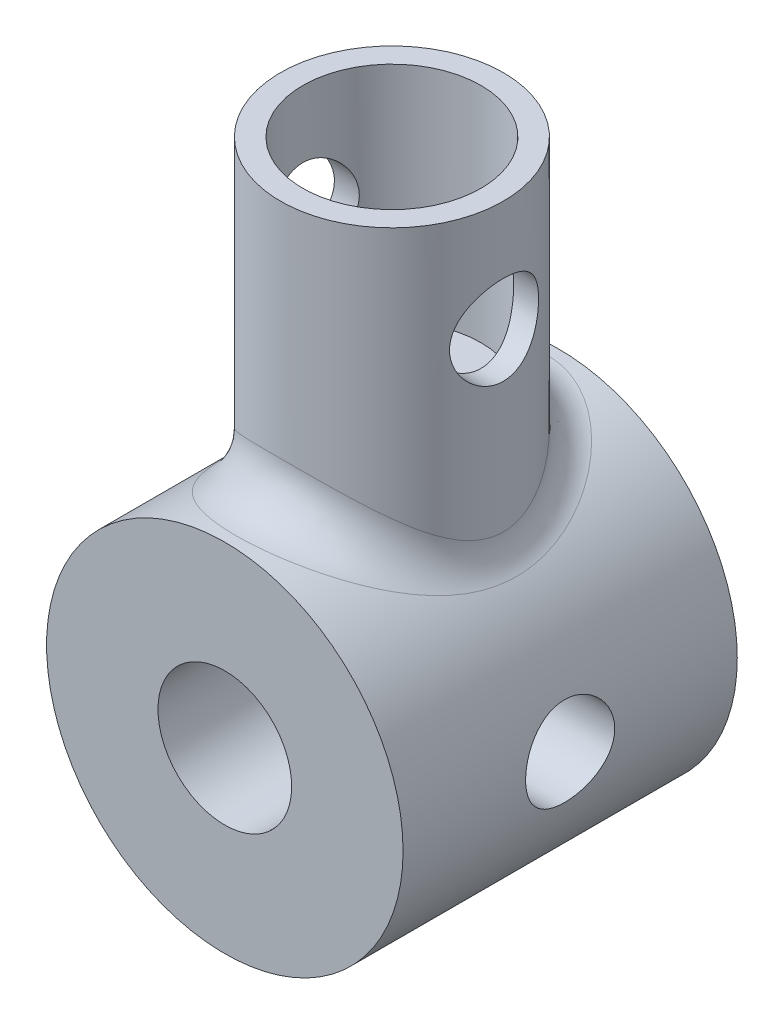
SolidWorks part; units mm, degrees
ref_plane "Front" through (0, 0, 0) normal (0, 0, 1) x (1, 0, 0)
ref_plane "Top" through (0, 0, 0) normal (0, 1, 0) x (1, 0, 0)
ref_plane "Right" through (0, 0, 0) normal (1, 0, 0) x (0, 0, -1)
sketch "Sketch1" plane through (0, 0, 0) normal (0, 0, 1) x (1, 0, 0)
  line L0 (0, 0) -> (0, 400) construction
  line L1 (-5, 0) -> (-5, 400)
  line L2 (5, 0) -> (5, 400)
  line L3 (0, -5) -> (0, 405)
  circle A0 centre (0, 0) radius 3
  circle A1 centre (0, 0) radius 8
  arc A2 (-5, 0) -> (5, 0) centre (0, 0) ccw
  arc A3 (5, 400) -> (-5, 400) centre (0, 400) ccw
  point P5 (0, 200)
  dimension "D1" = 6
  dimension "D4" = 5
  dimension "D3" = 400
  dimension "D2" = 5
extrude "Boss-Extrude1" add sketch "Sketch1" along normal mid plane 15 contours A2 L1 A1 L2 | L3 A2 L2 A1 A0 | L1 A2 L3 A0 A1 region at (-3.687, -3.687, 0) region at (-2.6489, 2.2826, 0) region at (2.6489, 2.2826, 0)
sketch "Sketch3" plane through (0, 0, 0) normal (0, 0, 1) x (1, 0, 0)
  line L1 (-10, 399) -> (10, 399)
  line L2 (-10, 399) -> (-10, 429)
  line L3 (-10, 429) -> (10, 429)
  line L4 (10, 399) -> (10, 429)
  line L5 (-10, 399) -> (10, 429) construction
  line L6 (-10, 429) -> (10, 399) construction
  point P0 (0, 414)
  dimension "D1" = 30
  dimension "D2" = 20
  dimension "D3" = 399
extrude "Boss-Extrude2" add sketch "Sketch3" along normal mid plane 15
revolve "Revolve2" add sketch "Sketch1<7>" angle 360 about L0 region at (2.4981, 205.6864, 0)
sketch "Sketch1<7>" plane through (0, 0, 0) normal (0, 0, 1) x (1, 0, 0) same geometry as "Sketch1"
combine bodies "Combine1" operation type add bodies to combine 106 101
fillet "Fillet1" radius 2 2 edges at (0, 399, 5) (1.219, 7.9066, 4.8491)
sketch "Sketch5" plane through (0, 429, 0) normal (0, 1, 0) x (1, 0, 0)
  line L0 (8, 5.5) -> (-8, 5.5)
  line L1 (-8, 5.5) -> (-8, -5.5)
  line L2 (-8, -5.5) -> (8, -5.5)
  line L3 (8, -5.5) -> (8, 5.5)
  line L4 (10, 7.5) -> (-10, 7.5)
  line L5 (-10, 7.5) -> (-10, -7.5)
  line L6 (-10, -7.5) -> (10, -7.5)
  line L7 (10, -7.5) -> (10, 7.5)
  line L8 (10, 7.5) -> (-10, 7.5)
  line L9 (-10, 7.5) -> (-10, -7.5)
  line L10 (-10, -7.5) -> (10, -7.5)
  line L11 (10, -7.5) -> (10, 7.5)
  dimension "D1" = 0
  dimension "D2" = 2
extrude "Cut-Extrude1" cut sketch "Sketch5" against normal blind 18 flip side to cut
sketch "Sketch6" plane through (0, 0, 0) normal (1, 0, 0) x (0, 0, -1)
  circle A0 centre (0, 0) radius 2
  dimension "D1" = 4
extrude "Cut-Extrude2" cut sketch "Sketch6" against normal through all both and the other way through all
sketch "Sketch7" [suppressed] plane through (0, 0, 0) normal (0, 0, 1) x (1, 0, 0)
  line L0 (-10, 399) -> (10, 399) construction
  line L1 (30.1951, -30.5023) -> (-25.142, -30.5023)
  line L2 (30.1951, -30.5023) -> (30.1951, 379)
  line L3 (30.1951, 379) -> (-25.142, 379)
  line L4 (-25.142, -30.5023) -> (-25.142, 379)
  dimension "D1" = 20
extrude "Cut-Extrude3" [suppressed] cut sketch "Sketch7" against normal through all both and the other way through all
sketch "Sketch8" [suppressed] plane through (0, 379, 0) normal (0, -1, 0) x (1, 0, 0)
  circle A0 centre (0, 0) radius 5 construction
  circle A1 centre (0, 0) radius 5
  circle A2 centre (0, 0) radius 4
  dimension "D1" = 1
extrude "Cut-Extrude4" [suppressed] cut sketch "Sketch8" against normal offset from surface 5 and the other way through all contours A2
sketch "Sketch9" [suppressed] plane through (-10, 0, 0) normal (-1, 0, 0) x (0, 0, 1)
  line L0 (7.5, 399) -> (-7.5, 399) construction
  circle A0 centre (0, 389) radius 2
  dimension "D1" = 4
  dimension "D2" = 10
extrude "Cut-Extrude5" [suppressed] cut sketch "Sketch9" against normal through all both and the other way through all
sketch "Sketch10" plane through (0, 0, 0) normal (0, 0, 1) x (1, 0, 0)
  line L1 (-34.1499, 436.6924) -> (68.4205, 436.6924)
  line L2 (-34.1499, 436.6924) -> (-34.1499, 20)
  line L3 (-34.1499, 20) -> (68.4205, 20)
  line L4 (68.4205, 436.6924) -> (68.4205, 20)
  dimension "D1" = 20
extrude "Cut-Extrude6" cut sketch "Sketch10" against normal through all both and the other way through all
sketch "Sketch11" plane through (0, 20, 0) normal (0, 1, 0) x (1, 0, 0)
  circle A0 centre (0, 0) radius 4
  circle A1 centre (0, 0) radius 5
  circle A2 centre (0, 0) radius 5
  dimension "D1" = 0
  dimension "D2" = 1
extrude "Cut-Extrude7" cut sketch "Sketch11" against normal blind 10 and the other way through all contours A0 region at (0, 20, 0)
sketch "Sketch12" plane through (0, 0, 0) normal (1, 0, 0) x (0, 0, -1)
  circle A1 centre (0, 15) radius 2
  dimension "D1" = 4
  dimension "D2" = 15
extrude "Cut-Extrude8" cut sketch "Sketch12" against normal through all both and the other way through all
